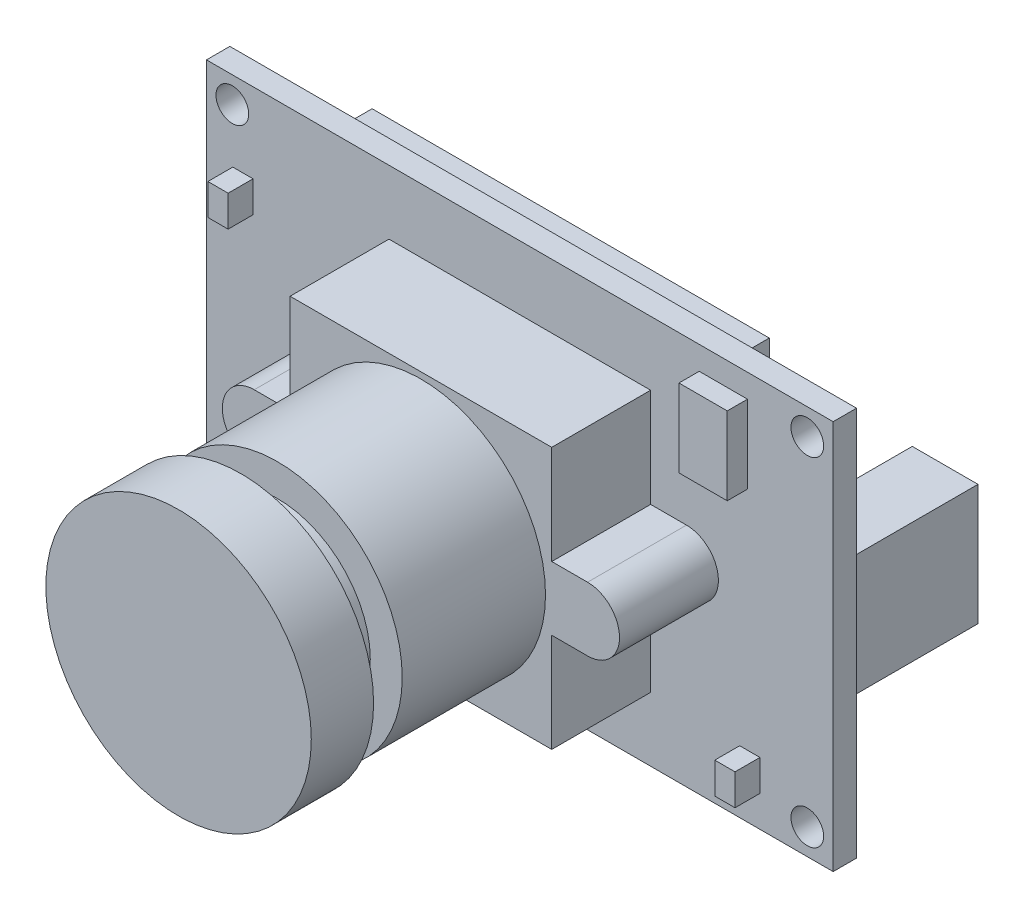
SolidWorks part; units mm, degrees
ref_plane "Front Plane" through (0, 0, 0) normal (0, 0, 1) x (1, 0, 0)
ref_plane "Top Plane" through (0, 0, 0) normal (0, 1, 0) x (1, 0, 0)
ref_plane "Right Plane" through (0, 0, 0) normal (1, 0, 0) x (0, 0, -1)
sketch "Sketch2" plane through (0, 0, 0) normal (0, 0, 1) x (1, 0, 0)
  line L0 (0, 0) -> (0, 6.003) construction
  line L1 (20.1168, 12.5095) -> (-20.1168, 12.5095)
  line L2 (20.1168, 12.5095) -> (20.1168, -12.5095)
  line L3 (20.1168, -12.5095) -> (-20.1168, -12.5095)
  line L4 (-20.1168, 12.5095) -> (-20.1168, -12.5095)
  line L5 (20.1168, 12.5095) -> (-20.1168, -12.5095) construction
  line L6 (20.1168, -12.5095) -> (-20.1168, 12.5095) construction
  line L7 (-1000, 0) -> (49000, 0) construction
  circle A0 centre (-18.4568, 10.8495) radius 1.05
  circle A1 centre (-18.4568, -10.8495) radius 1.05
  circle A2 centre (18.4568, -10.8495) radius 1.05
  circle A3 centre (18.4568, 10.8495) radius 1.05
  point P0 (0, 0)
  dimension "D5" = 2.1
  dimension "D1" = 40.2336
  dimension "D2" = 25.019
  dimension "D3" = 1.66
  dimension "D4" = 1.66
extrude "Boss-Extrude1" add sketch "Sketch2" along normal blind 1.5
sketch "Sketch3" plane through (0, 0, 1.5) normal (0, 0, 1) x (1, 0, 0)
  line L0 (-8.4, -2.05) -> (-8.4, -8.4)
  line L1 (8.4, 8.4) -> (-8.4, 8.4)
  line L2 (8.4, 8.4) -> (8.4, 2.05)
  line L3 (8.4, -8.4) -> (-8.4, -8.4)
  line L4 (-8.4, 8.4) -> (-8.4, 2.05)
  line L5 (8.4, 8.4) -> (-8.4, -8.4) construction
  line L6 (8.4, -8.4) -> (-8.4, 8.4) construction
  line L7 (-10.7, 2.05) -> (-8.4, 2.05)
  line L8 (0, -1000) -> (0, 49000) construction
  line L9 (-10.7, -2.05) -> (-8.4, -2.05)
  line L10 (10.7, 2.05) -> (8.4, 2.05)
  line L11 (10.7, -2.05) -> (8.4, -2.05)
  line L12 (8.4, -2.05) -> (8.4, -8.4)
  line L13 (-1000, 0) -> (49000, 0) construction
  arc A0 (-10.7, 2.05) -> (-10.7, -2.05) centre (-10.7, 0) ccw
  arc A1 (10.7, 2.05) -> (10.7, -2.05) centre (10.7, 0) cw
  point P0 (0, 0)
  dimension "D1" = 16.8
  dimension "D2" = 16.8
  dimension "D3" = 4.1
  dimension "D4" = 2.3
extrude "Boss-Extrude2" add sketch "Sketch3" along normal blind 6.35
sketch "Sketch4" plane through (0, 0, 7.85) normal (0, 0, 1) x (1, 0, 0)
  circle A0 centre (0, 0) radius 8
  dimension "D1" = 16
extrude "Boss-Extrude3" add sketch "Sketch4" along normal blind 9.2
sketch "Sketch5" plane through (0, 0, 17.05) normal (0, 0, 1) x (1, 0, 0)
  circle A0 centre (0, 0) radius 5.95
  dimension "D1" = 11.9
extrude "Boss-Extrude4" add sketch "Sketch5" along normal blind 2.36
sketch "Sketch6" plane through (0, 0, 19.41) normal (0, 0, 1) x (1, 0, 0)
  circle A0 centre (0, 0) radius 8.5217
  dimension "D1" = 17.0434
extrude "Lens" add sketch "Sketch6" along normal blind 4
sketch "Sketch7" plane through (0, 0, 0) normal (0, 0, -1) x (-1, 0, 0)
  line L0 (0, 0) -> (-20.1168, 0) construction
  line L1 (-15.3968, -3.875) -> (-19.6168, -3.875)
  line L2 (-15.3968, -3.875) -> (-15.3968, 3.875)
  line L3 (-15.3968, 3.875) -> (-19.6168, 3.875)
  line L4 (-19.6168, -3.875) -> (-19.6168, 3.875)
  line L5 (-20.1168, -12.5095) -> (-20.1168, 12.5095) construction
  point P9 (-19.6168, 0)
  dimension "D1" = 7.75
  dimension "D2" = 4.22
  dimension "D3" = 0.5
extrude "Boss-Extrude6" add sketch "Sketch7" along normal blind 8.3
sketch "Sketch8" plane through (0, 0, 0) normal (0, 0, -1) x (-1, 0, 0)
  line L0 (20.1168, 12.5095) -> (20.1168, -12.5095) construction
  line L1 (15.6768, -10.8695) -> (6.6768, -10.8695)
  line L2 (15.6768, -10.8695) -> (15.6768, -7.9395)
  line L3 (15.6768, -7.9395) -> (6.6768, -7.9395)
  line L4 (6.6768, -10.8695) -> (6.6768, -7.9395)
  line L5 (20.1168, -12.5095) -> (-20.1168, -12.5095) construction
  dimension "D1" = 4.44
  dimension "D2" = 1.64
  dimension "D3" = 9
  dimension "D4" = 2.93
extrude "Boss-Extrude7" add sketch "Sketch8" along normal blind 4.35
sketch "Sketch9" plane through (0, 0, 1.5) normal (0, 0, 1) x (1, 0, 0)
  line L0 (20.1168, -12.5095) -> (20.1168, 12.5095) construction
  line L1 (11.5168, 11.0095) -> (14.6168, 11.0095)
  line L2 (11.5168, 11.0095) -> (11.5168, 6.0095)
  line L3 (11.5168, 6.0095) -> (14.6168, 6.0095)
  line L4 (14.6168, 11.0095) -> (14.6168, 6.0095)
  line L5 (20.1168, 12.5095) -> (-20.1168, 12.5095) construction
  dimension "D1" = 3.1
  dimension "D2" = 5
  dimension "D3" = 5.5
  dimension "D4" = 1.5
extrude "Boss-Extrude8" add sketch "Sketch9" along normal blind 1.3
sketch "Sketch10" plane through (0, 0, 0) normal (0, 0, -1) x (-1, 0, 0)
  line L0 (-20.1168, -12.5095) -> (-20.1168, 12.5095) construction
  line L1 (-13.1168, 12.2095) -> (12.3832, 12.2095)
  line L2 (-13.1168, 12.2095) -> (-13.1168, 4.2095)
  line L3 (-13.1168, 4.2095) -> (12.3832, 4.2095)
  line L4 (12.3832, 12.2095) -> (12.3832, 4.2095)
  line L5 (-13.1168, 12.2095) -> (12.3832, 4.2095) construction
  line L6 (-13.1168, 4.2095) -> (12.3832, 12.2095) construction
  line L7 (-20.1168, 12.5095) -> (20.1168, 12.5095) construction
  point P0 (-0.3668, 8.2095)
  dimension "D1" = 25.5
  dimension "D2" = 8
  dimension "D3" = 7
  dimension "D4" = 0.3
extrude "Boss-Extrude9" add sketch "Sketch10" along normal blind 1.4
sketch "Sketch11" plane through (0, 0, 1.5) normal (0, 0, 1) x (1, 0, 0)
  line L0 (20.1168, -12.5095) -> (20.1168, 12.5095) construction
  line L1 (15.4168, -10.5095) -> (14.1168, -10.5095)
  line L2 (15.4168, -10.5095) -> (15.4168, -8.5095)
  line L3 (15.4168, -8.5095) -> (14.1168, -8.5095)
  line L4 (14.1168, -10.5095) -> (14.1168, -8.5095)
  line L5 (-20.1168, -12.5095) -> (20.1168, -12.5095) construction
  line L6 (-17.1271, 5.3916) -> (-18.4271, 5.3916)
  line L7 (-17.1271, 5.3916) -> (-17.1271, 7.3916)
  line L8 (-17.1271, 7.3916) -> (-18.4271, 7.3916)
  line L9 (-18.4271, 5.3916) -> (-18.4271, 7.3916)
  dimension "D1" = 1.3
  dimension "D2" = 2
  dimension "D3" = 6
  dimension "D4" = 2
extrude "Boss-Extrude10" add sketch "Sketch11" along normal blind 1.6
sketch "Sketch12" plane through (0, 0, 0) normal (0, 0, -1) x (-1, 0, 0)
  line L0 (-20.1168, 12.5095) -> (20.1168, 12.5095) construction
  line L1 (19.1168, 5.1095) -> (16.1168, 5.1095)
  line L2 (19.1168, 5.1095) -> (19.1168, 8.1095)
  line L3 (19.1168, 8.1095) -> (16.1168, 8.1095)
  line L4 (16.1168, 5.1095) -> (16.1168, 8.1095)
  line L5 (20.1168, 12.5095) -> (20.1168, -12.5095) construction
  dimension "D1" = 3
  dimension "D2" = 3
  dimension "D3" = 7.4
  dimension "D4" = 1
extrude "Boss-Extrude11" add sketch "Sketch12" along normal blind 1.4
sketch "Sketch13" plane through (0, 0, 0) normal (0, 0, -1) x (-1, 0, 0)
  line L0 (-20.1168, -12.5095) -> (-20.1168, 12.5095) construction
  line L1 (-14.1478, -9.3853) -> (-10.9728, -9.3853)
  line L2 (-14.1478, -9.3853) -> (-14.1478, -12.0015)
  line L3 (-14.1478, -12.0015) -> (-10.9728, -12.0015)
  line L4 (-10.9728, -9.3853) -> (-10.9728, -12.0015)
  line L5 (20.1168, -12.5095) -> (-20.1168, -12.5095) construction
  line L7 (-7.1628, -7.1755) -> (1.3462, -7.1755)
  line L8 (-7.1628, -7.1755) -> (-7.1628, -12.0015)
  line L9 (-7.1628, -12.0015) -> (1.3462, -12.0015)
  line L10 (1.3462, -7.1755) -> (1.3462, -12.0015)
  dimension "D1" = 3.175
  dimension "D2" = 2.6162
  dimension "D3" = 5.969
  dimension "D4" = 0.508
  dimension "D5" = 8.509
  dimension "D6" = 4.826
  dimension "D7" = 12.954
  dimension "D8" = 0.508
extrude "Boss-Extrude12" add sketch "Sketch13" along normal blind 2.7432
move or copy body "Body-Move/Copy1" [suppressed] bodies to move or copy 112
